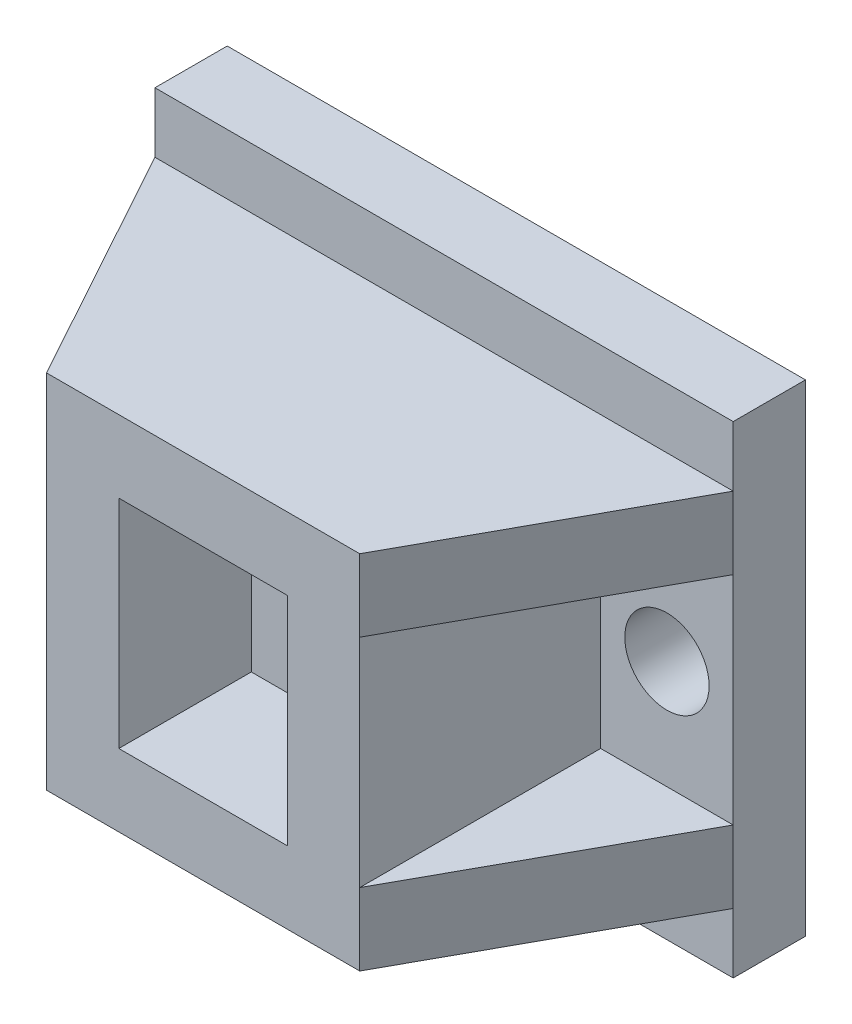
SolidWorks part; units mm, degrees
ref_plane "Plan de face" through (0, 0, 0) normal (0, 0, 1) x (1, 0, 0)
ref_plane "Plan de dessus" through (0, 0, 0) normal (0, 1, 0) x (1, 0, 0)
ref_plane "Plan de droite" through (0, 0, 0) normal (1, 0, 0) x (0, 0, -1)
sketch "Esquisse1" plane through (0, 0, 0) normal (0, 0, 1) x (1, 0, 0)
  line L0 (-6.5, 7.5) -> (-6.5, -7.5)
  line L1 (-3.5, 4.5) -> (3.5, 4.5)
  line L2 (-3.5, 4.5) -> (-3.5, -4.5)
  line L3 (-3.5, -4.5) -> (3.5, -4.5)
  line L4 (3.5, 4.5) -> (3.5, -4.5)
  line L5 (-6.5, -7.5) -> (6.5, -7.5)
  line L6 (6.5, 7.5) -> (6.5, -7.5)
  line L7 (-6.5, 7.5) -> (6.5, 7.5)
  line L12 (-9.25, 0) -> (-12, 0) construction
  line L13 (-12, 10) -> (12, 10)
  line L14 (-12, 10) -> (-12, -10)
  line L15 (-12, -10) -> (12, -10)
  line L16 (12, 10) -> (12, -10)
  line L17 (-9.25, 0) -> (-6.5, 0) construction
  line L18 (9.25, 0) -> (6.5, 0) construction
  line L19 (9.25, 0) -> (12, 0) construction
  circle A0 centre (-9.25, 0) radius 1.75
  circle A1 centre (9.25, 0) radius 1.75
  point P8 (0, 4.5)
  point P10 (-3.5, 0)
  point P15 (-12, 0)
  point P16 (0, -10)
  dimension "D5" = 20
  dimension "D6" = 3.5
  dimension "D1" = 3
  dimension "D2" = 7
  dimension "D3" = 9
  dimension "D4" = 24
extrude "Boss.-Extru.1" add sketch "Esquisse1" along normal blind 3 contours L13 L15 L0 L7 L6 L5 region at (0, 9.6876, 0)
extrude "Boss.-Extru.2" add sketch "Esquisse1<3>" along normal blind 13 contours L7 L0 L5 L6 L1 L4 L3 L2 region at (0, 7.3015, 0)
sketch "Esquisse1<3>" plane through (0, 0, 0) normal (0, 0, 1) x (1, 0, 0) same geometry as "Esquisse1"
sketch "Esquisse5" plane through (0, -7.5, 0) normal (0, -1, 0) x (1, 0, 0)
  line L0 (-6.5, 13) -> (-12, 3)
rib "Nervure2" sketch "Esquisse5" sketch "Esquisse5" thickness 3 extrusion direction parallel to sketch draft on no parameters "D1"=3
mirror "Symétrie4" about plane through (0, 0, 0) normal (0, 1, 0) of "Nervure2"
mirror "Symétrie5" about plane through (0, 0, 0) normal (1, 0, 0) of "Nervure2", "Symétrie4"
extrude "Boss.-Extru.3" add sketch "Esquisse1<4>" along normal blind 7.5 contours L4 L1 L2 L3 region at (0, 0, 0)
sketch "Esquisse1<4>" plane through (0, 0, 0) normal (0, 0, 1) x (1, 0, 0) same geometry as "Esquisse1"
